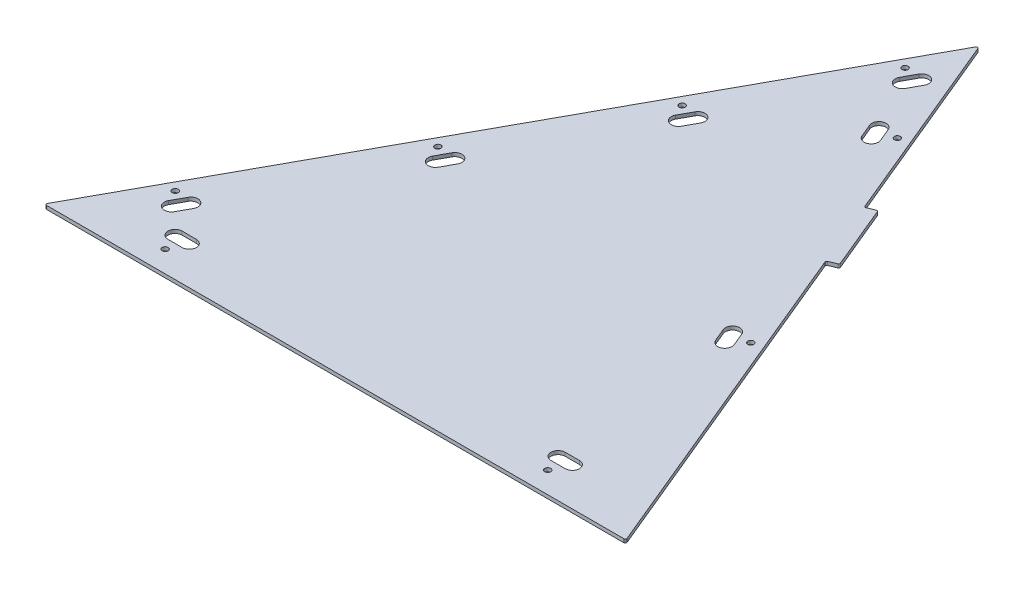
SolidWorks part; units mm, degrees
material "PE High Density"
ref_plane "Front Plane" through (0, 0, 0) normal (0, 0, 1) x (1, 0, 0)
ref_plane "Top Plane" through (0, 0, 0) normal (0, 1, 0) x (1, 0, 0)
ref_plane "Right Plane" through (0, 0, 0) normal (1, 0, 0) x (0, 0, -1)
sketch "Sketch4" plane through (0, 0, 0) normal (0, 1, 0) x (1, 0, 0)
  line L0 (-356.1703, 0) -> (682.6897, 0)
  line L1 (682.6897, 0) -> (234.9792, 1078.9716)
  line L2 (234.9792, 1078.9716) -> (-356.1703, 0)
  line L3 (381.0003, 727.0642) -> (398.5957, 734.3653)
  line L4 (398.5957, 734.3653) -> (447.2694, 617.0628)
  line L5 (447.2694, 617.0628) -> (429.674, 609.7617)
  line L6 (429.674, 609.7617) -> (381.0003, 727.0642)
  line L9 (664.3232, 0) -> (-326.0136, 0) construction
  circle A2 centre (303.6675, 863.7291) radius 5.3578
  circle A3 centre (489.2933, 416.3753) radius 5.3578
  circle A5 centre (61.0945, 721.9489) radius 5.3578
  circle A6 centre (-93.2898, 440.1652) radius 5.3578
  circle A7 centre (-259.301, 137.16) radius 5.3578
  circle A9 centre (504.8897, 38.1) radius 5.3578
  circle A10 centre (-178.3703, 38.1) radius 5.3578
  circle A11 centre (201.9739, 979.0832) radius 5.3578
  dimension "D4" = 10.7156
  dimension "D5" = 19.05
  dimension "D6" = 10.7156
  dimension "D10" = 10.7156
  dimension "D12" = 10.7156
  dimension "D13" = 127
  dimension "D14" = 10.7156
  dimension "D15" = 10.7156
  dimension "D16" = 10.7156
  dimension "D1" = 1038.86
  dimension "D2" = 1168.1714
  dimension "D3" = 1230.2998
  dimension "D7" = 19.05
  dimension "D8" = 19.05
  dimension "D9" = 19.05
  dimension "D11" = 38.1
  dimension "D17" = 137.16
  dimension "D18" = 381
  dimension "D20" = 38.1
  dimension "D21" = 177.8
  dimension "D22" = 19.05
  dimension "D23" = 19.05
  dimension "D24" = 177.8
  dimension "D25" = 19.05
extrude "Boss-Extrude2" add sketch "Sketch4" along normal blind 6.35 contours L2 L0 L1 A9 A7 A6 A5 A3 A2 | L6 L3 L4 L5 region at (187.2415, 0, -359.5352)
sketch "Sketch5" plane through (0, 6.35, 0) normal (0, 1, 0) x (1, 0, 0)
  line L0 (-239.2238, 110.3702) -> (-227.0193, 132.6459) construction
  line L1 (-250.3617, 116.4724) -> (-238.1571, 138.7482)
  line L2 (-228.0859, 104.2679) -> (-215.8814, 126.5437)
  line L3 (-191.0703, 68.58) -> (-165.6703, 68.58) construction
  line L4 (-191.0703, 81.28) -> (-165.6703, 81.28)
  line L5 (-191.0703, 55.88) -> (-165.6703, 55.88)
  line L6 (-72.3558, 414.9391) -> (-60.1513, 437.2149) construction
  line L7 (-83.4937, 421.0413) -> (-71.2892, 443.3171)
  line L8 (-61.2179, 408.8368) -> (-49.0134, 431.1126)
  line L9 (222.745, 953.5599) -> (234.9496, 975.8357) construction
  line L10 (211.6072, 959.6622) -> (223.8117, 981.9379)
  line L11 (233.8829, 947.4576) -> (246.0874, 969.7334)
  line L12 (81.2069, 695.2231) -> (93.4668, 717.6001) construction
  line L13 (70.069, 701.3254) -> (82.3289, 723.7023)
  line L14 (92.3448, 689.1209) -> (104.6047, 711.4978)
  line L15 (270.6329, 863.8128) -> (280.3677, 840.3524) construction
  line L18 (456.0343, 416.9998) -> (465.7691, 393.5393) construction
  line L19 (467.7646, 421.8672) -> (477.4993, 398.4067)
  line L20 (444.3041, 412.1325) -> (454.0388, 388.672)
  line L21 (492.9613, 68.58) -> (518.3613, 68.58) construction
  line L22 (492.9613, 81.28) -> (518.3613, 81.28)
  line L23 (492.9613, 55.88) -> (518.3613, 55.88)
  line L24 (234.9792, 1078.9716) -> (-356.1703, 0) construction
  line L25 (-356.1703, 0) -> (682.6897, 0) construction
  line L26 (282.3632, 868.6802) -> (292.0979, 845.2197)
  line L27 (258.9027, 858.9455) -> (268.6374, 835.485)
  line L28 (682.6897, 0) -> (429.674, 609.7617) construction
  line L29 (381.0003, 727.0642) -> (234.9792, 1078.9716) construction
  arc A0 (-250.3617, 116.4724) -> (-228.0859, 104.2679) centre (-239.2238, 110.3702) ccw
  arc A1 (-215.8814, 126.5437) -> (-238.1571, 138.7482) centre (-227.0193, 132.6459) ccw
  arc A2 (-191.0703, 81.28) -> (-191.0703, 55.88) centre (-191.0703, 68.58) ccw
  arc A3 (-165.6703, 55.88) -> (-165.6703, 81.28) centre (-165.6703, 68.58) ccw
  arc A4 (-83.4937, 421.0413) -> (-61.2179, 408.8368) centre (-72.3558, 414.9391) ccw
  arc A5 (-49.0134, 431.1126) -> (-71.2892, 443.3171) centre (-60.1513, 437.2149) ccw
  arc A6 (211.6072, 959.6622) -> (233.8829, 947.4576) centre (222.745, 953.5599) ccw
  arc A7 (246.0874, 969.7334) -> (223.8117, 981.9379) centre (234.9496, 975.8357) ccw
  arc A8 (70.069, 701.3254) -> (92.3448, 689.1209) centre (81.2069, 695.2231) ccw
  arc A9 (104.6047, 711.4978) -> (82.3289, 723.7023) centre (93.4668, 717.6001) ccw
  arc A12 (467.7646, 421.8672) -> (444.3041, 412.1325) centre (456.0343, 416.9998) ccw
  arc A13 (454.0388, 388.672) -> (477.4993, 398.4067) centre (465.7691, 393.5393) ccw
  arc A14 (492.9613, 81.28) -> (492.9613, 55.88) centre (492.9613, 68.58) ccw
  arc A15 (518.3613, 55.88) -> (518.3613, 81.28) centre (518.3613, 68.58) ccw
  circle A16 centre (-178.3703, 38.1) radius 5.3578 construction
  circle A17 centre (-259.301, 137.16) radius 5.3578 construction
  circle A18 centre (-93.2898, 440.1652) radius 5.3578 construction
  arc A19 (282.3632, 868.6802) -> (258.9027, 858.9455) centre (270.6329, 863.8128) ccw
  circle A20 centre (61.0945, 721.9489) radius 5.3578 construction
  arc A22 (268.6374, 835.485) -> (292.0979, 845.2197) centre (280.3677, 840.3524) ccw
  circle A23 centre (489.2933, 416.3753) radius 5.3578 construction
  circle A24 centre (504.8897, 38.1) radius 5.3578 construction
  circle A25 centre (201.9739, 979.0832) radius 5.3578 construction
  circle A26 centre (303.6675, 863.7291) radius 5.3578 construction
  point P2 (-233.1215, 121.5081)
  point P7 (-178.3703, 68.58)
  point P14 (-66.2536, 426.077)
  point P21 (228.8473, 964.6978)
  point P28 (87.3369, 706.4116)
  point P35 (275.5003, 852.0826)
  point P42 (460.9017, 405.2696)
  point P49 (505.6613, 68.58)
  dimension "D9" = 17.78
  dimension "D10" = 17.78
  dimension "D6" = 17.78
  dimension "D1" = 25.4
  dimension "D2" = 25.4
  dimension "D3" = 17.78
  dimension "D4" = 17.78
  dimension "D5" = 17.78
  dimension "D7" = 17.78
  dimension "D8" = 17.78
  dimension "D11" = 121.5081
  dimension "D12" = 426.077
  dimension "D13" = 706.4116
  dimension "D14" = 114.2738
  dimension "D15" = 405.2696
extrude "Cut-Extrude1" cut sketch "Sketch5" against normal through all
fillet "Fillet1" radius 2.54 7 edges at (398.5957, 3.175, -734.3653) (447.2694, 3.175, -617.0628) (429.674, 3.175, -609.7617) (381.0003, 3.175, -727.0642) (682.6897, 3.175, 0) (-356.1703, 3.175, 0) (234.9792, 3.175, -1078.9716)
